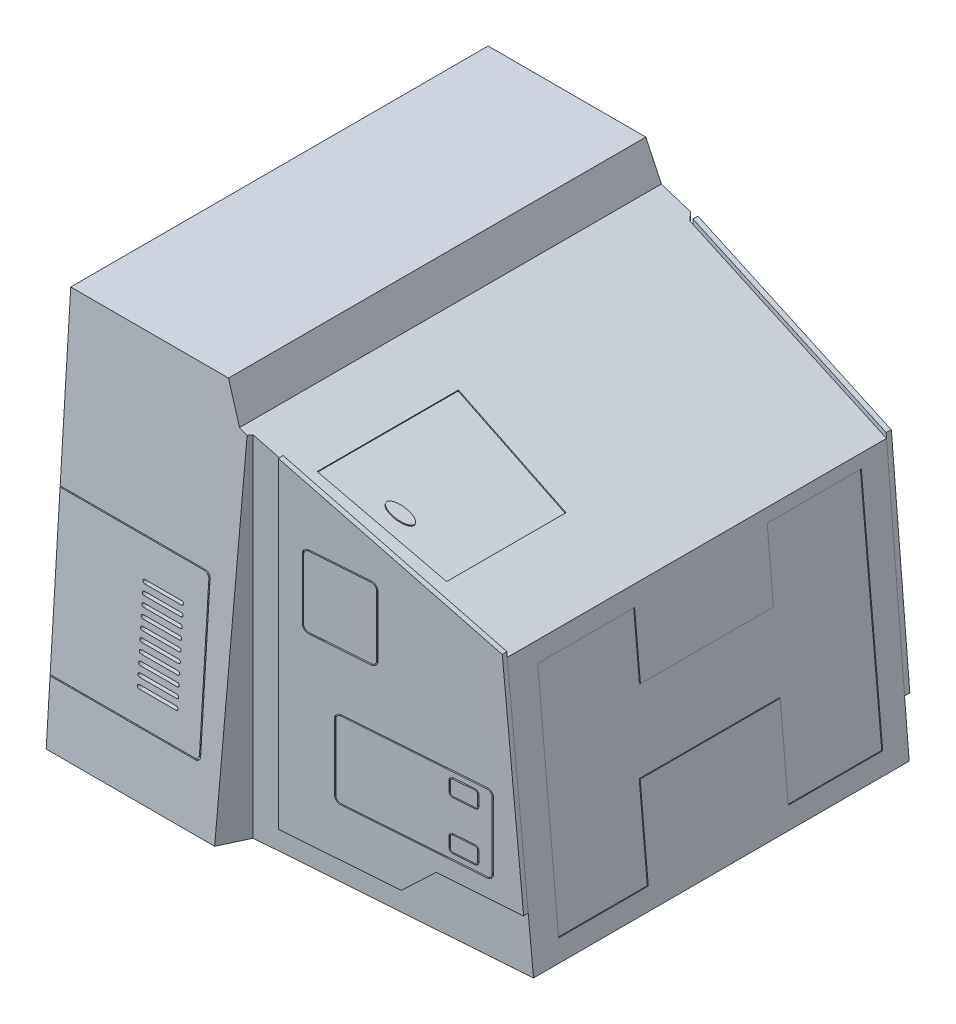
SolidWorks part; units mm, degrees
ref_plane "Front Plane" through (0, 0, 0) normal (0, 0, 1) x (1, 0, 0)
ref_plane "Top Plane" through (0, 0, 0) normal (0, 1, 0) x (1, 0, 0)
ref_plane "Right Plane" through (0, 0, 0) normal (1, 0, 0) x (0, 0, -1)
sketch "Sketch3" plane through (0, 0, 0) normal (0, 1, 0) x (1, 0, 0)
  line L1 (-180, 95) -> (180, 95)
  line L2 (-180, 95) -> (-180, -95)
  line L3 (-180, -95) -> (180, -95)
  line L4 (180, 95) -> (180, -95)
  line L5 (-180, 95) -> (180, -95) construction
  line L6 (-180, -95) -> (180, 95) construction
  point P0 (0, 0)
  dimension "D1" = 190
  dimension "D2" = 360
extrude "Boss-Extrude2" add sketch "Sketch3" along normal blind 158
sketch "Sketch4" plane through (180, 0, 0) normal (1, 0, 0) x (0, 0, -1)
  line L0 (-95, 0) -> (-95, 158)
  line L1 (-95, 158) -> (-85, 158)
  line L2 (-95, 158) -> (95, 158) construction
  line L3 (-85, 158) -> (-95, 0)
  line L4 (0, 0) -> (0, 123.75) construction
  line L5 (85, 158) -> (95, 0)
  line L6 (95, 158) -> (85, 158)
  line L7 (95, 0) -> (95, 158)
  dimension "D1" = 170
extrude "Cut-Extrude1" cut sketch "Sketch4" against normal through all
sketch "Sketch5" plane through (0, 0, 0) normal (0, 0, 1) x (1, 0, 0)
  line L0 (-180, 0) -> (-165.5, 158)
  line L1 (-180, 158) -> (180, 158) construction
  line L2 (-165.5, 158) -> (-180, 158)
  line L3 (-180, 158) -> (-180, 0)
  line L4 (0, 0) -> (0, 158) construction
  line L5 (180, 158) -> (180, 0)
  line L6 (165.5, 158) -> (180, 158)
  line L7 (180, 0) -> (165.5, 158)
  dimension "D1" = 331
extrude "Cut-Extrude2" cut sketch "Sketch5" against normal through all both and the other way through all
sketch "Sketch6" plane through (0, 0, 0) normal (0, 0, 1) x (1, 0, 0)
  line L0 (180, 0) -> (180, 105) construction
  line L2 (-165.5, 158) -> (165.5, 158) construction
  line L3 (64, 145.6686) -> (180, 105)
  line L4 (180, 105) -> (180, 158)
  line L5 (-180, 110) -> (-180, 158)
  line L6 (-180, 158) -> (-97, 158)
  line L8 (-180, 0) -> (-180, 110) construction
  line L9 (64, 145.6686) -> (64, 158)
  line L10 (64, 158) -> (180, 158)
  line L11 (-180, 110) -> (-97, 145.6686)
  line L12 (-97, 145.6686) -> (-97, 158)
  dimension "D1" = 105
  dimension "D2" = 110
  dimension "D3" = 83
  dimension "D4" = 116
extrude "Cut-Extrude3" cut sketch "Sketch6" along normal through all both and the other way through all
sketch "Sketch8" plane through (0, 0, 0) normal (0, 1, 0) x (1, 0, 0)
  line L0 (-180, 76.5) -> (-97, 85)
  line L3 (-180, 95) -> (-180, -95) construction
  line L4 (-180, 111.8161) -> (-180, 76.5)
  line L5 (0, 0) -> (-198.7212, 0) construction
  line L11 (-180, 111.8161) -> (-97, 111.8161)
  line L12 (-97, 111.8161) -> (-97, 85)
  line L13 (-97, -111.8161) -> (-97, -85)
  line L14 (-180, -111.8161) -> (-97, -111.8161)
  line L15 (-180, -111.8161) -> (-180, -76.5)
  line L16 (-180, -76.5) -> (-97, -85)
  line L17 (64, 85) -> (64, 140.1812)
  line L18 (64, 85) -> (180, 76.5)
  line L19 (180, 76.5) -> (197.104, 166.0233)
  line L20 (197.104, 166.0233) -> (64, 140.1812)
  line L21 (197.104, -166.0233) -> (64, -140.1812)
  line L22 (180, -76.5) -> (197.104, -166.0233)
  line L23 (64, -85) -> (180, -76.5)
  line L24 (64, -85) -> (64, -140.1812)
  line L29 (180, -95) -> (180, 95) construction
  dimension "D1" = 153
extrude "Cut-Extrude4" cut sketch "Sketch8" against normal through all and the other way through all
sketch "Sketch10" plane through (0, 0, 0) normal (0, -1, 0) x (1, 0, 0)
  line L1 (-156.5, -79) -> (156.5, -79) construction
  line L2 (-156.5, -79) -> (-156.5, 79) construction
  line L3 (-156.5, 79) -> (156.5, 79) construction
  line L4 (156.5, -79) -> (156.5, 79) construction
  line L5 (-156.5, -79) -> (156.5, 79) construction
  line L6 (-156.5, 79) -> (156.5, -79) construction
  point P0 (0, 0)
  dimension "D1" = 313
  dimension "D2" = 158
shell "Shell6" thickness 5 removed face at (-11, 0, 0)
sketch "Sketch11" plane through (0, 0, 0) normal (0, -1, 0) x (1, 0, 0)
  line L0 (-97, 95) -> (64, 95) construction
  line L1 (-97, 95) -> (64, 95)
  line L14 (-97, 95) -> (-97, 85)
  line L15 (-97, 85) -> (-180, 76.5)
  line L16 (-180, 76.5) -> (-180, -76.5)
  line L17 (-180, -76.5) -> (-97, -85)
  line L18 (-97, -85) -> (-97, -95)
  line L19 (-97, -95) -> (64, -95)
  line L20 (64, -95) -> (64, -85)
  line L21 (64, -85) -> (180, -76.5)
  line L22 (180, -76.5) -> (180, 76.5)
  line L23 (180, 76.5) -> (64, 85)
  line L24 (64, 85) -> (64, 95)
  line L25 (64, 95) -> (-97, 95)
  line L26 (-97, 95) -> (-97, 85)
  line L27 (-97, 85) -> (-180, 76.5)
  line L28 (-180, 76.5) -> (-180, -76.5)
  line L29 (-180, -76.5) -> (-97, -85)
  line L30 (-97, -85) -> (-97, -95)
  line L31 (-97, -95) -> (64, -95)
  line L32 (64, -95) -> (64, -85)
  line L33 (64, -85) -> (180, -76.5)
  line L34 (180, -76.5) -> (180, 76.5)
  line L35 (180, 76.5) -> (64, 85)
  line L36 (64, 85) -> (64, 95)
  line L37 (64, 95) -> (-97, 95)
  line M25 (-92, 80.4859) -> (-92, 89.99)
  line M26 (-92, 89.99) -> (59, 89.99)
  line M27 (59, 89.99) -> (59, 80.353)
  line M28 (59, 80.353) -> (174.979, 71.8545)
  line M29 (174.979, 71.8545) -> (174.979, -71.8545)
  line M30 (174.979, -71.8545) -> (59, -80.353)
  line M31 (59, -80.353) -> (59, -89.99)
  line M32 (59, -89.99) -> (-92, -89.99)
  line M33 (-92, -89.99) -> (-92, -80.4859)
  line M34 (-92, -80.4859) -> (-174.979, -71.988)
  line M35 (-174.979, -71.988) -> (-174.979, 71.988)
  line M36 (-174.979, 71.988) -> (-92, 80.4859)
  dimension "D1" = 0
extrude "Boss-Extrude3" add sketch "Sketch11" against normal blind 5 contours M25 M36 M35 M34 M33 M32 M31 M30 M29 M28 M27 M26 region at (-1.4169, 0, 0)
chamfer "Chamfer1" distance 19.9 angle 25 2 edges at (-97, 72.8343, -85) (64, 72.8343, 85) first distance on face at (-97, 75.9172, 0) first distance on face at (64, 75.9172, 0)
chamfer "Chamfer2" distance 19.9 angle 25 2 edges at (-97, 72.8343, 85) (64, 72.8343, -85) first distance on face at (-97, 101.2229, 29.8699) first distance on face at (64, 101.2229, -29.8699)
chamfer "Chamfer3" distance 10 angle 45 2 edges at (73.6078, 71.1501, -84.296) (-106.7449, 70.7404, 84.002) first distance on face at (124.3148, 62.6977, -80.5804) first distance on face at (-140.7451, 63.9993, 80.5201)
chamfer "Chamfer4" distance 5 angle 50 1 edges at (-97, 145.6686, 0) first distance on face at (-122.0326, 134.911, -0.0994)
chamfer "Chamfer5" distance 6 angle 50 1 edges at (64, 145.6686, 0) first distance on face at (97.4296, 133.9485, 0.0677)
sketch "Sketch18" plane through (-9.6212, 0, 93.9484) normal (-0.1019, 0, 0.9948) x (0.9948, 0, 0.1019)
  line L0 (-160.4966, 116.7807) -> (-170.6066, 7.1902)
  line L1 (-171.2699, 0) -> (-160.7055, 114.5163) construction
  line L2 (-170.6066, 7.1902) -> (-129.9277, 7.1902)
  line L3 (-129.9277, 7.1902) -> (-126.2803, 17.3621)
  line L4 (-126.2803, 17.3621) -> (-115.3442, 17.3621)
  line L5 (-115.3442, 17.3621) -> (-115.3442, 136.0837)
  line L7 (-115.3442, 136.0837) -> (-160.4966, 116.7807)
  line L11 (-107.6316, 0) -> (-171.2699, 0) construction
  line L12 (-107.6316, 0) -> (-107.6316, 137.2058) construction
  line L14 (-107.6316, 137.2058) -> (-160.7055, 114.5163) construction
  dimension "D1" = 2
extrude "Boss-Extrude5" add sketch "Sketch18" along normal blind 2
sketch "Sketch19" plane through (-9.825, 0, 95.938) normal (-0.1019, 0, 0.9948) x (0.9948, 0, 0.1019)
  line L0 (-144.8175, 92.3146) -> (-144.8175, 71.3428)
  line L1 (-143.3175, 94.3146) -> (-122.3457, 94.3146)
  line L2 (-145.3175, 92.3146) -> (-145.3175, 71.3428)
  line L3 (-143.3175, 69.3428) -> (-122.3457, 69.3428)
  line L4 (-120.3457, 92.3146) -> (-120.3457, 71.3428)
  line L5 (-145.3175, 94.3146) -> (-122.3457, 69.3428) construction
  line L6 (-145.3175, 69.3428) -> (-120.3457, 94.3146) construction
  line L7 (-143.3175, 69.8428) -> (-122.3457, 69.8428)
  line L8 (-120.8457, 92.3146) -> (-120.8457, 71.3428)
  line L9 (-143.3175, 93.8146) -> (-122.3457, 93.8146)
  arc A0 (-122.3457, 94.3146) -> (-120.3457, 92.3146) centre (-122.3457, 92.3146) cw
  arc A1 (-122.3457, 69.3428) -> (-120.3457, 71.3428) centre (-122.3457, 71.3428) ccw
  arc A2 (-145.3175, 71.3428) -> (-143.3175, 69.3428) centre (-143.3175, 71.3428) ccw
  arc A3 (-143.3175, 94.3146) -> (-145.3175, 92.3146) centre (-143.3175, 92.3146) ccw
  arc A4 (-144.8175, 71.3428) -> (-143.3175, 69.8428) centre (-143.3175, 71.3428) ccw
  arc A5 (-122.3457, 69.8428) -> (-120.8457, 71.3428) centre (-122.3457, 71.3428) ccw
  arc A6 (-122.3457, 93.8146) -> (-120.8457, 92.3146) centre (-122.3457, 92.3146) cw
  arc A7 (-143.3175, 93.8146) -> (-144.8175, 92.3146) centre (-143.3175, 92.3146) ccw
  point P0 (-133.3524, 81.3079)
  dimension "D1" = 2
  dimension "D2" = 0.5
extrude "Cut-Extrude5" cut sketch "Sketch19" against normal blind 0.5
sketch "Sketch20" plane through (0, 5.9887, 94.621) normal (0, 0.0632, 0.998) x (1, 0, 0)
  line L0 (-89.2026, 82.2629) -> (-89.2026, 21.0896)
  line L1 (-86.7026, 83.7629) -> (58.7101, 83.7629)
  line L2 (-88.7026, 81.7629) -> (-88.7026, 21.5896)
  line L3 (-86.7026, 19.5896) -> (58.7101, 19.5896)
  line L4 (60.7101, 81.7629) -> (60.7101, 21.5896)
  line L5 (-88.7026, 83.7629) -> (60.7101, 19.5896) construction
  line L6 (-88.7026, 19.5896) -> (60.7101, 83.7629) construction
  line L7 (-87.2026, 19.0896) -> (59.2101, 19.0896)
  line L8 (61.2101, 82.2629) -> (61.2101, 21.0896)
  line L9 (-87.2026, 84.2629) -> (59.2101, 84.2629)
  line L10 (61.2101, 84.2629) -> (61.2101, 19.0896) construction
  line L11 (-89.2026, 84.2629) -> (61.2101, 84.2629) construction
  line L12 (-88.7026, 83.7629) -> (60.7101, 83.7629) construction
  line L13 (60.7101, 83.7629) -> (60.7101, 19.5896) construction
  line L14 (-88.7026, 19.5896) -> (60.7101, 19.5896) construction
  line L15 (-89.2026, 19.0896) -> (61.2101, 19.0896) construction
  line L16 (-89.2026, 84.2629) -> (-89.2026, 19.0896) construction
  line L17 (-88.7026, 83.7629) -> (-88.7026, 19.5896) construction
  arc A0 (61.2101, 82.2629) -> (59.2101, 84.2629) centre (59.2101, 82.2629) ccw
  arc A1 (58.7101, 83.7629) -> (60.7101, 81.7629) centre (58.7101, 81.7629) cw
  arc A2 (58.7101, 19.5896) -> (60.7101, 21.5896) centre (58.7101, 21.5896) ccw
  arc A3 (59.2101, 19.0896) -> (61.2101, 21.0896) centre (59.2101, 21.0896) ccw
  arc A4 (-89.2026, 21.0896) -> (-87.2026, 19.0896) centre (-87.2026, 21.0896) ccw
  arc A5 (-88.7026, 21.5896) -> (-86.7026, 19.5896) centre (-86.7026, 21.5896) ccw
  arc A6 (-89.2026, 82.2629) -> (-87.2026, 84.2629) centre (-87.2026, 82.2629) cw
  arc A7 (-86.7026, 83.7629) -> (-88.7026, 81.7629) centre (-86.7026, 81.7629) ccw
  point P0 (-13.9963, 51.6763)
  dimension "D2" = 2
  dimension "D1" = 0.5
extrude "Cut-Extrude6" cut sketch "Sketch20" against normal blind 0.5
sketch "Sketch21" plane through (6.537, 0, 89.2107) normal (0.0731, 0, 0.9973) x (0.9973, 0, -0.0731)
  line L0 (78.6105, 140.2638) -> (78.6105, 9.5077)
  line L2 (163.945, 108.4906) -> (173.9281, 0) construction
  line L3 (171.9049, 21.987) -> (163.7609, 110.4906)
  line L4 (163.7609, 110.4906) -> (78.6105, 140.2638)
  line L6 (67.2506, 142.3002) -> (67.2506, 0) construction
  line L8 (78.6105, 9.5077) -> (125.3303, 9.5077)
  line L9 (125.3303, 9.5077) -> (138.5436, 21.987)
  line L10 (138.5436, 21.987) -> (171.9049, 21.987)
  line L11 (163.945, 108.4906) -> (67.2506, 142.3002) construction
  line L12 (163.945, 108.4906) -> (175.2328, 108.4906) construction
  dimension "D1" = 2
extrude "Boss-Extrude6" add sketch "Sketch21" along normal blind 2
sketch "Sketch22" plane through (6.6831, 0, 91.2053) normal (0.0731, 0, 0.9973) x (0.9973, 0, -0.0731)
  line L0 (99.9186, 58.3939) -> (99.9186, 31.5005)
  line L1 (90.1817, 112.8938) -> (113.9275, 112.8938)
  line L2 (88.1817, 110.8938) -> (88.1817, 86.2383)
  line L3 (90.1817, 84.2383) -> (113.9275, 84.2383)
  line L4 (115.9275, 110.8938) -> (115.9275, 86.2383)
  line L5 (88.1817, 112.8938) -> (115.9275, 84.2383) construction
  line L6 (88.1817, 84.2383) -> (115.9275, 112.8938) construction
  line L7 (102.4186, 60.3939) -> (157.9396, 60.3939)
  line L8 (100.4186, 58.3939) -> (100.4186, 31.5005)
  line L9 (102.4186, 29.5005) -> (157.9396, 29.5005)
  line L10 (159.9396, 58.3939) -> (159.9396, 31.5005)
  line L11 (100.4186, 60.3939) -> (159.9396, 29.5005) construction
  line L12 (100.4186, 29.5005) -> (159.9396, 60.3939) construction
  line L13 (144.9909, 57.8533) -> (153.382, 57.8533)
  line L14 (143.9909, 56.8533) -> (143.9909, 52.772)
  line L15 (144.9909, 51.772) -> (153.382, 51.772)
  line L16 (154.382, 56.8533) -> (154.382, 52.772)
  line L17 (143.9909, 57.8533) -> (154.382, 51.772) construction
  line L18 (143.9909, 51.772) -> (154.382, 57.8533) construction
  line L19 (144.9909, 38.1224) -> (153.382, 38.1224)
  line L20 (143.9909, 37.1224) -> (143.9909, 33.0411)
  line L21 (144.9909, 32.0411) -> (153.382, 32.0411)
  line L22 (154.382, 37.1224) -> (154.382, 33.0411)
  line L23 (143.9909, 38.1224) -> (154.382, 32.0411) construction
  line L24 (143.9909, 32.0411) -> (154.382, 38.1224) construction
  line L25 (102.4186, 29.0005) -> (157.9396, 29.0005)
  line L26 (160.4396, 58.3939) -> (160.4396, 31.5005)
  line L27 (102.4186, 60.8939) -> (157.9396, 60.8939)
  line L28 (87.6817, 110.8938) -> (87.6817, 86.2383)
  line L29 (90.1817, 83.7383) -> (113.9275, 83.7383)
  line L30 (116.4275, 110.8938) -> (116.4275, 86.2383)
  line L31 (90.1817, 113.3938) -> (113.9275, 113.3938)
  line L32 (143.4909, 56.8533) -> (143.4909, 52.772)
  line L33 (144.9909, 51.272) -> (153.382, 51.272)
  line L34 (154.882, 56.8533) -> (154.882, 52.772)
  line L35 (144.9909, 58.3533) -> (153.382, 58.3533)
  line L36 (143.4909, 37.1224) -> (143.4909, 33.0411)
  line L37 (144.9909, 31.5411) -> (153.382, 31.5411)
  line L38 (154.882, 37.1224) -> (154.882, 33.0411)
  line L39 (144.9909, 38.6224) -> (153.382, 38.6224)
  arc A0 (157.9396, 60.3939) -> (159.9396, 58.3939) centre (157.9396, 58.3939) cw
  arc A1 (157.9396, 29.5005) -> (159.9396, 31.5005) centre (157.9396, 31.5005) ccw
  arc A2 (100.4186, 31.5005) -> (102.4186, 29.5005) centre (102.4186, 31.5005) ccw
  arc A3 (102.4186, 60.3939) -> (100.4186, 58.3939) centre (102.4186, 58.3939) ccw
  arc A4 (113.9275, 112.8938) -> (115.9275, 110.8938) centre (113.9275, 110.8938) cw
  arc A5 (113.9275, 84.2383) -> (115.9275, 86.2383) centre (113.9275, 86.2383) ccw
  arc A6 (88.1817, 86.2383) -> (90.1817, 84.2383) centre (90.1817, 86.2383) ccw
  arc A7 (90.1817, 112.8938) -> (88.1817, 110.8938) centre (90.1817, 110.8938) ccw
  arc A8 (143.9909, 33.0411) -> (144.9909, 32.0411) centre (144.9909, 33.0411) ccw
  arc A9 (153.382, 38.1224) -> (154.382, 37.1224) centre (153.382, 37.1224) cw
  arc A10 (153.382, 32.0411) -> (154.382, 33.0411) centre (153.382, 33.0411) ccw
  arc A11 (144.9909, 38.1224) -> (143.9909, 37.1224) centre (144.9909, 37.1224) ccw
  arc A12 (143.9909, 52.772) -> (144.9909, 51.772) centre (144.9909, 52.772) ccw
  arc A13 (153.382, 51.772) -> (154.382, 52.772) centre (153.382, 52.772) ccw
  arc A14 (153.382, 57.8533) -> (154.382, 56.8533) centre (153.382, 56.8533) cw
  arc A15 (144.9909, 57.8533) -> (143.9909, 56.8533) centre (144.9909, 56.8533) ccw
  arc A16 (99.9186, 31.5005) -> (102.4186, 29.0005) centre (102.4186, 31.5005) ccw
  arc A17 (157.9396, 29.0005) -> (160.4396, 31.5005) centre (157.9396, 31.5005) ccw
  arc A18 (157.9396, 60.8939) -> (160.4396, 58.3939) centre (157.9396, 58.3939) cw
  arc A19 (102.4186, 60.8939) -> (99.9186, 58.3939) centre (102.4186, 58.3939) ccw
  arc A20 (87.6817, 86.2383) -> (90.1817, 83.7383) centre (90.1817, 86.2383) ccw
  arc A21 (113.9275, 83.7383) -> (116.4275, 86.2383) centre (113.9275, 86.2383) ccw
  arc A22 (113.9275, 113.3938) -> (116.4275, 110.8938) centre (113.9275, 110.8938) cw
  arc A23 (90.1817, 113.3938) -> (87.6817, 110.8938) centre (90.1817, 110.8938) ccw
  arc A24 (143.4909, 52.772) -> (144.9909, 51.272) centre (144.9909, 52.772) ccw
  arc A25 (153.382, 51.272) -> (154.882, 52.772) centre (153.382, 52.772) ccw
  arc A26 (153.382, 58.3533) -> (154.882, 56.8533) centre (153.382, 56.8533) cw
  arc A27 (144.9909, 58.3533) -> (143.4909, 56.8533) centre (144.9909, 56.8533) ccw
  arc A28 (143.4909, 33.0411) -> (144.9909, 31.5411) centre (144.9909, 33.0411) ccw
  arc A29 (153.382, 31.5411) -> (154.882, 33.0411) centre (153.382, 33.0411) ccw
  arc A30 (153.382, 38.6224) -> (154.882, 37.1224) centre (153.382, 37.1224) cw
  arc A31 (144.9909, 38.6224) -> (143.4909, 37.1224) centre (144.9909, 37.1224) ccw
  point P0 (102.0546, 98.566)
  point P5 (130.1791, 44.9472)
  point P10 (149.1865, 35.0818)
  point P11 (149.1865, 54.8126)
  dimension "D1" = 2
  dimension "D2" = 1
  dimension "D3" = 0.5
  dimension "D4" = 0.5
  dimension "D5" = 0.5
  dimension "D6" = 0.5
extrude "Cut-Extrude7" cut sketch "Sketch22" against normal blind 0.5 contours L31 A23 L28 A20 L29 A21 L30 A22 A7 L1 A4 L4 A5 L3 A6 L2 | L27 A19 L0 A16 L25 A17 L26 A18 A3 L7 A0 L10 A1 L9 A2 L8 | L35 A27 L32 A24 L33 A25 L34 A26 A15 L13 A14 L16 A13 L15 A12 L14 | L39 A31 L36 A28 L37 A29 L38 A30 A11 L19 A9 L22 A10 L21 A8 L20 region at (107.1131, 60.1133, 83.8462) region at (95.152, 112.3695, 84.7227) region at (150.3231, 57.8191, 80.68) region at (150.3231, 38.0882, 80.68)
sketch "Sketch23" plane through (0, 5.9887, 94.621) normal (0, 0.0632, 0.998) x (1, 0, 0)
  line L0 (35.4779, 68.5836) -> (50.4779, 68.5836) construction
  line L1 (35.4779, 69.3336) -> (50.4779, 69.3336)
  line L2 (35.4779, 67.8336) -> (50.4779, 67.8336)
  line L3 (42.9779, 68.5836) -> (42.9779, 41.1335) construction
  line L4 (35.4779, 64.5836) -> (50.4779, 64.5836) construction
  line L5 (35.4779, 65.3336) -> (50.4779, 65.3336)
  line L6 (35.4779, 63.8336) -> (50.4779, 63.8336)
  line L7 (35.4779, 60.5836) -> (50.4779, 60.5836) construction
  line L8 (35.4779, 61.3336) -> (50.4779, 61.3336)
  line L9 (35.4779, 59.8336) -> (50.4779, 59.8336)
  line L10 (35.4779, 56.5836) -> (50.4779, 56.5836) construction
  line L11 (35.4779, 57.3336) -> (50.4779, 57.3336)
  line L12 (35.4779, 55.8336) -> (50.4779, 55.8336)
  line L13 (35.4779, 52.5836) -> (50.4779, 52.5836) construction
  line L14 (35.4779, 53.3336) -> (50.4779, 53.3336)
  line L15 (35.4779, 51.8336) -> (50.4779, 51.8336)
  line L16 (35.4779, 48.5836) -> (50.4779, 48.5836) construction
  line L17 (35.4779, 49.3336) -> (50.4779, 49.3336)
  line L18 (35.4779, 47.8336) -> (50.4779, 47.8336)
  line L19 (35.4779, 44.5836) -> (50.4779, 44.5836) construction
  line L20 (35.4779, 45.3336) -> (50.4779, 45.3336)
  line L21 (35.4779, 43.8336) -> (50.4779, 43.8336)
  line L22 (35.4779, 40.5836) -> (50.4779, 40.5836) construction
  line L23 (35.4779, 41.3336) -> (50.4779, 41.3336)
  line L24 (35.4779, 39.8336) -> (50.4779, 39.8336)
  line L25 (35.4779, 36.5836) -> (50.4779, 36.5836) construction
  line L26 (35.4779, 37.3336) -> (50.4779, 37.3336)
  line L27 (35.4779, 35.8336) -> (50.4779, 35.8336)
  line L28 (35.4779, 32.5836) -> (50.4779, 32.5836) construction
  line L29 (35.4779, 33.3336) -> (50.4779, 33.3336)
  line L30 (35.4779, 31.8336) -> (50.4779, 31.8336)
  arc A0 (35.4779, 69.3336) -> (35.4779, 67.8336) centre (35.4779, 68.5836) ccw
  arc A1 (50.4779, 67.8336) -> (50.4779, 69.3336) centre (50.4779, 68.5836) ccw
  arc A2 (35.4779, 65.3336) -> (35.4779, 63.8336) centre (35.4779, 64.5836) ccw
  arc A3 (50.4779, 63.8336) -> (50.4779, 65.3336) centre (50.4779, 64.5836) ccw
  arc A4 (35.4779, 61.3336) -> (35.4779, 59.8336) centre (35.4779, 60.5836) ccw
  arc A5 (50.4779, 59.8336) -> (50.4779, 61.3336) centre (50.4779, 60.5836) ccw
  arc A6 (35.4779, 57.3336) -> (35.4779, 55.8336) centre (35.4779, 56.5836) ccw
  arc A7 (50.4779, 55.8336) -> (50.4779, 57.3336) centre (50.4779, 56.5836) ccw
  arc A8 (35.4779, 53.3336) -> (35.4779, 51.8336) centre (35.4779, 52.5836) ccw
  arc A9 (50.4779, 51.8336) -> (50.4779, 53.3336) centre (50.4779, 52.5836) ccw
  arc A10 (35.4779, 49.3336) -> (35.4779, 47.8336) centre (35.4779, 48.5836) ccw
  arc A11 (50.4779, 47.8336) -> (50.4779, 49.3336) centre (50.4779, 48.5836) ccw
  arc A12 (35.4779, 45.3336) -> (35.4779, 43.8336) centre (35.4779, 44.5836) ccw
  arc A13 (50.4779, 43.8336) -> (50.4779, 45.3336) centre (50.4779, 44.5836) ccw
  arc A14 (35.4779, 41.3336) -> (35.4779, 39.8336) centre (35.4779, 40.5836) ccw
  arc A15 (50.4779, 39.8336) -> (50.4779, 41.3336) centre (50.4779, 40.5836) ccw
  arc A16 (35.4779, 37.3336) -> (35.4779, 35.8336) centre (35.4779, 36.5836) ccw
  arc A17 (50.4779, 35.8336) -> (50.4779, 37.3336) centre (50.4779, 36.5836) ccw
  arc A18 (35.4779, 33.3336) -> (35.4779, 31.8336) centre (35.4779, 32.5836) ccw
  arc A19 (50.4779, 31.8336) -> (50.4779, 33.3336) centre (50.4779, 32.5836) ccw
  point P2 (42.9779, 68.5836)
  point P9 (42.9779, 68.5836)
  point P13 (42.9779, 64.5836)
  point P20 (42.9779, 60.5836)
  point P27 (42.9779, 56.5836)
  point P34 (42.9779, 52.5836)
  point P41 (42.9779, 48.5836)
  point P48 (42.9779, 44.5836)
  point P55 (42.9779, 40.5836)
  point P62 (42.9779, 36.5836)
  point P69 (42.9779, 32.5836)
  dimension "D1" = 1.5
  dimension "D2" = 15
  dimension "D4" = 4
  dimension "D3" = 10
extrude "Cut-Extrude8" cut sketch "Sketch23" against normal up to next
sketch "Sketch24" plane through (-132.805, 39.9565, 0) normal (-0.9576, 0.2881, 0) x (0, 0, 1)
  line L0 (0, 0) -> (0, 138.6299) construction
  line L1 (-70.0038, 121.648) -> (-70.0038, 110.9297)
  line L2 (-74.0038, 121.648) -> (-22.0038, 121.648)
  line L3 (-74.0038, 121.648) -> (-74.0038, 110.9297)
  line L4 (-74.0038, 110.9297) -> (-22.0038, 110.9297)
  line L5 (-22.0038, 121.648) -> (-22.0038, 110.9297)
  line L6 (-74.0038, 121.648) -> (-22.0038, 110.9297) construction
  line L7 (-74.0038, 110.9297) -> (-22.0038, 121.648) construction
  line L8 (-66.0038, 121.648) -> (-66.0038, 110.9297)
  line L9 (-62.0038, 121.648) -> (-62.0038, 110.9297)
  line L10 (-58.0038, 121.648) -> (-58.0038, 110.9297)
  line L11 (-54.0038, 121.648) -> (-54.0038, 110.9297)
  line L12 (-50.0038, 121.648) -> (-50.0038, 110.9297)
  line L13 (-46.0038, 121.648) -> (-46.0038, 110.9297)
  line L14 (-42.0038, 121.648) -> (-42.0038, 110.9297)
  line L15 (-38.0038, 121.648) -> (-38.0038, 110.9297)
  line L16 (-34.0038, 121.648) -> (-34.0038, 110.9297)
  line L17 (-30.0038, 121.648) -> (-30.0038, 110.9297)
  line L18 (-26.0038, 121.648) -> (-26.0038, 110.9297)
  line L19 (-22.0038, 121.648) -> (-22.0038, 110.9297)
  point P3 (-48.0038, 116.2888)
  dimension "D2" = 52
  dimension "D3" = 4
  dimension "D4" = 4
  dimension "D1" = 13
extrude "Cut-Extrude9" cut sketch "Sketch24" against normal up to next contours L3 L4 L1 L2 | L9 L2 L8 L4 | L11 L2 L10 L4 | L13 L2 L12 L4 | L15 L2 L14 L4 | L17 L2 L16 L4 | L2 L18 L4 L5
mirror "Mirror1" about plane through (0, 0, 0) normal (0, 0, 1) of "Cut-Extrude9", "Cut-Extrude7", "Cut-Extrude6", "Cut-Extrude5", "Boss-Extrude5", "Boss-Extrude6", "Cut-Extrude8"
sketch "Sketch25" plane through (-178.4967, 16.381, 0) normal (-0.9958, 0.0914, 0) x (0, 0, 1)
  line L12 (-73.5279, -13.4499) -> (73.5279, -13.4499)
  line L13 (73.5677, -9.2014) -> (74.5481, 95.5477)
  line L14 (74.5481, 95.5477) -> (-74.5481, 95.5477)
  line L15 (-74.5481, 95.5477) -> (-73.5677, -9.2014)
  line L16 (-73.5279, -13.4499) -> (73.5279, -13.4499)
  line L17 (73.5677, -9.2014) -> (74.5481, 95.5477)
  line L18 (74.5481, 95.5477) -> (-74.5481, 95.5477)
  line L19 (-74.5481, 95.5477) -> (-73.5677, -9.2014)
  line L20 (73.5279, -13.4499) -> (73.5677, -9.2014)
  line L21 (73.5279, -13.4499) -> (73.5677, -9.2014)
  line L22 (-73.5677, -9.2014) -> (-73.5279, -13.4499)
  line L23 (-73.5677, -9.2014) -> (-73.5279, -13.4499)
  dimension "D1" = 3
extrude "Cut-Extrude10" cut sketch "Sketch25" against normal blind 1
sketch "Sketch26" plane through (52.4855, 149.7055, 0) normal (0.3308, 0.9437, 0) x (0.9437, -0.3308, 0)
  line L0 (93.9118, -72.9864) -> (93.9118, -24.3785)
  line L5 (93.9118, -24.3785) -> (42.7728, -19.9044)
  line L6 (42.7728, -19.9044) -> (42.7728, -77.4604)
  line L8 (42.7728, -77.4604) -> (93.9118, -72.9864)
  ellipse E0 centre (67.5901, -66.9324) end of major axis (62.2316, -67.5868) minor radius 2.6176
  dimension "D1" = 95
extrude "Cut-Extrude11" cut sketch "Sketch26" against normal blind 0.5 contours L6 L8 L0 L5 E0 region at (116.3016, 127.3321, 48.379)
sketch "Sketch29" plane through (178.4967, 16.381, 0) normal (0.9958, 0.0914, 0) x (0, 0, -1)
  line L0 (-65.5393, 84.8137) -> (-65.5393, -8.1386)
  line L1 (-65.5393, -8.1386) -> (-28.9885, -8.1386)
  line L2 (-28.9885, -8.1386) -> (-28.9885, 28.097)
  line L3 (-28.9885, 28.097) -> (28.0432, 28.097)
  line L4 (28.0432, 28.097) -> (28.0432, -8.1386)
  line L5 (28.0432, -8.1386) -> (66.4845, -8.1386)
  line L6 (66.4845, -8.1386) -> (66.4845, 87.3345)
  line L7 (66.4845, 87.3345) -> (28.1238, 87.3345)
  line L8 (28.1238, 87.3345) -> (28.1238, 58.9761)
  line L9 (28.1238, 58.9761) -> (-26.0721, 58.9761)
  line L10 (-26.0721, 58.9761) -> (-26.0721, 84.8137)
  line L11 (-26.0721, 84.8137) -> (-65.5393, 84.8137)
extrude "Cut-Extrude12" cut sketch "Sketch29" against normal blind 0.4
sketch "Sketch31" plane through (0, 0, 0) normal (0, 0, 1) x (1, 0, 0)
  line L1 (0, 0) -> (215.7861, 0)
  line L2 (0, 0) -> (0, 167.887)
  line L3 (0, 167.887) -> (215.7861, 167.887)
  line L4 (215.7861, 0) -> (215.7861, 167.887)
  point P4 (0, 0)
  point P6 (215.7861, 167.887)
sketch "Sketch32" plane through (0, 0, 0) normal (0, 0, 1) x (1, 0, 0)
  line L1 (0, 0) -> (-188.9502, 0)
  line L2 (0, 0) -> (0, 184.6213)
  line L3 (0, 184.6213) -> (-188.9502, 184.6213)
  line L4 (-188.9502, 0) -> (-188.9502, 184.6213)
extrude "Cut-Extrude14" cut sketch "Sketch32" against normal through all both and the other way through all
